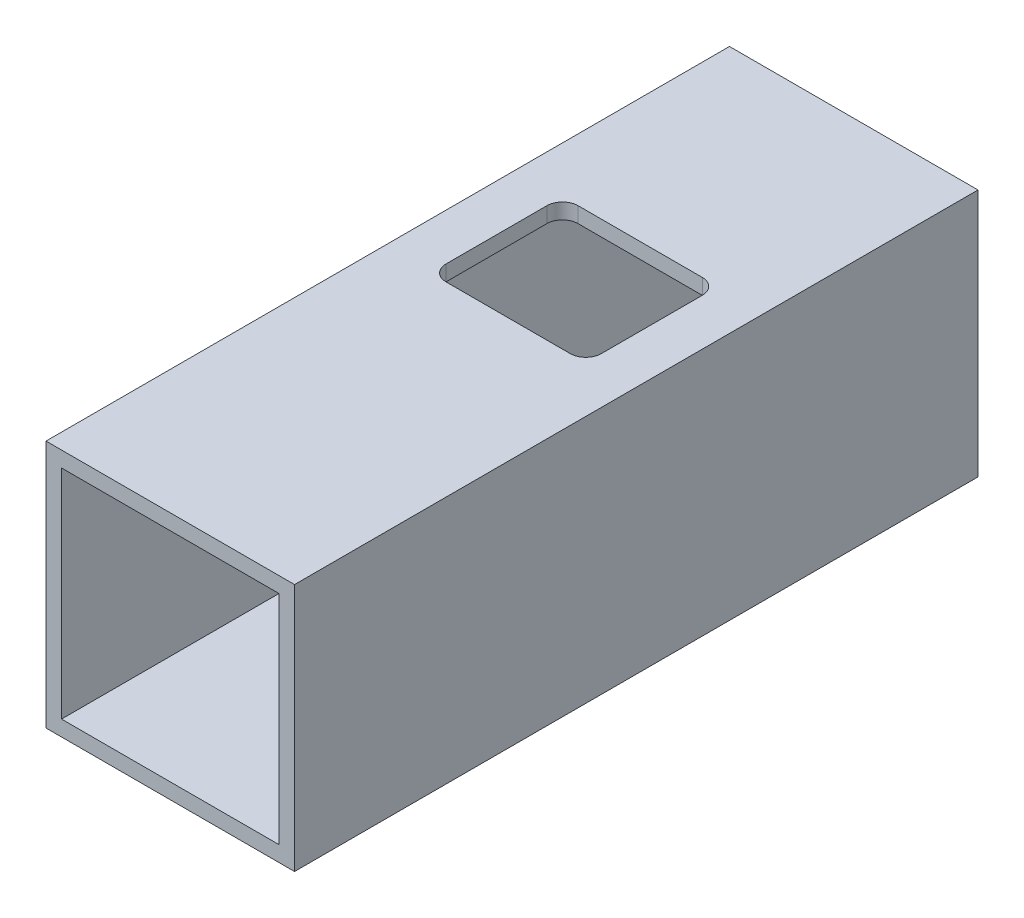
SolidWorks part; units mm, degrees
ref_plane "Front Plane" through (0, 0, 0) normal (0, 0, 1) x (1, 0, 0)
ref_plane "Top Plane" through (0, 0, 0) normal (0, 1, 0) x (1, 0, 0)
ref_plane "Right Plane" through (0, 0, 0) normal (1, 0, 0) x (0, 0, -1)
sketch "Sketch1" plane through (0, 0, 0) normal (0, 0, 1) x (1, 0, 0)
  line L1 (-25.4, -25.4) -> (25.4, -25.4)
  line L2 (-25.4, -25.4) -> (-25.4, 25.4)
  line L3 (-25.4, 25.4) -> (25.4, 25.4)
  line L4 (25.4, -25.4) -> (25.4, 25.4)
  line L5 (-25.4, -25.4) -> (25.4, 25.4) construction
  line L6 (-25.4, 25.4) -> (25.4, -25.4) construction
  point P0 (0, 0)
  dimension "D1" = 50.8
  dimension "D2" = 50.8
extrude "Boss-Extrude1" add sketch "Sketch1" along normal mid plane 139.7
shell "Shell1" thickness 3.175 removed face at (0, 0, -69.85) removed face at (0, 0, 69.85)
sketch "Sketch2" plane through (0, 0, 0) normal (0, 1, 0) x (1, 0, 0)
  line L0 (25.4, 69.85) -> (-25.4, 69.85) construction
  line L1 (15.875, 26.1938) -> (-15.875, 26.1938)
  line L2 (15.875, 26.1938) -> (15.875, -0.7937)
  line L3 (15.875, -0.7937) -> (-15.875, -0.7937)
  line L4 (-15.875, 26.1938) -> (-15.875, -0.7937)
  line L5 (25.4, -69.85) -> (-25.4, -69.85) construction
  point P4 (0, 26.1938)
  point P7 (0, 69.85)
  point P8 (15.875, 38.9214)
  point P9 (15.875, 12.7)
  dimension "D1" = 31.75
  dimension "D2" = 26.9875
  dimension "D3" = 82.55
extrude "Cut-Extrude1" cut sketch "Sketch2" along normal through all
fillet "Fillet1" radius 3.175 4 edges at (15.875, 23.8125, -26.1938) (-15.875, 23.8125, -26.1938) (-15.875, 23.8125, 0.7937) (15.875, 23.8125, 0.7937)
